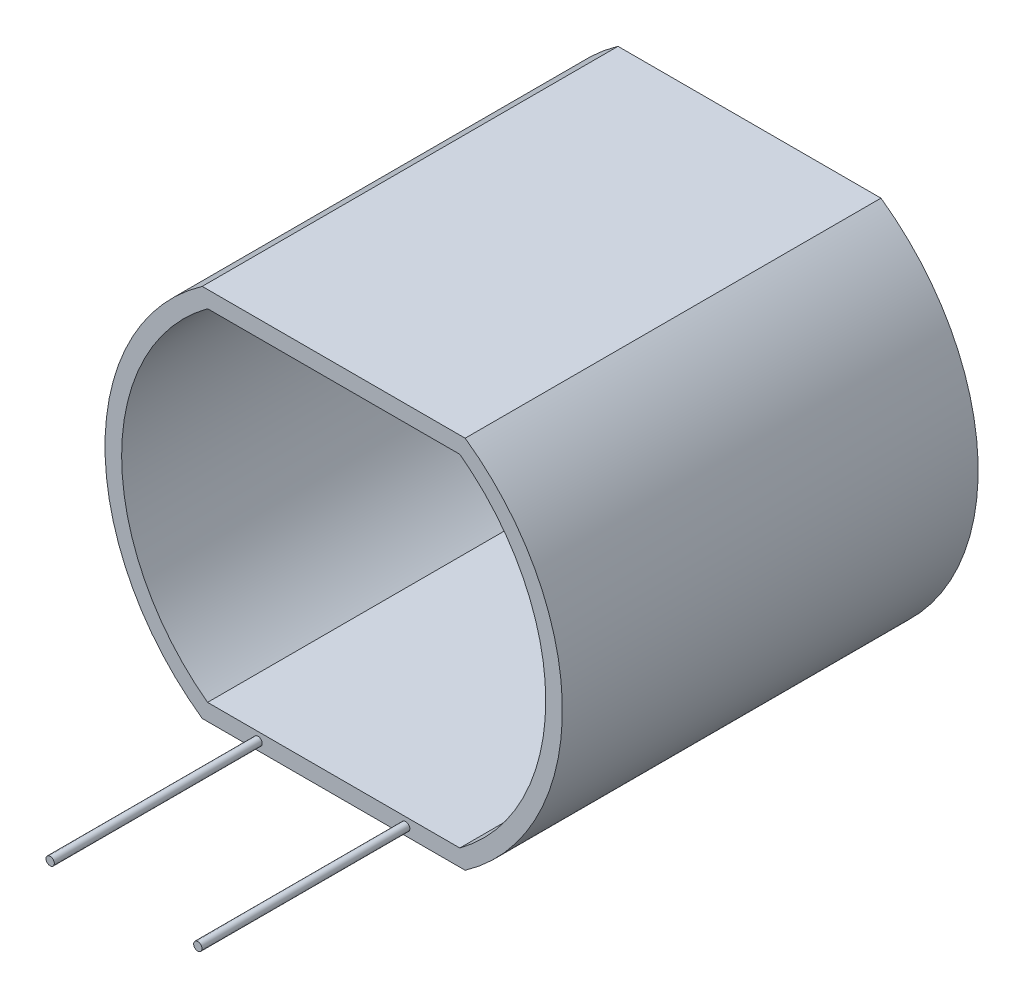
SolidWorks part; units mm, degrees
ref_plane "Front Plane" through (0, 0, 0) normal (0, 0, 1) x (1, 0, 0)
ref_plane "Top Plane" through (0, 0, 0) normal (0, 1, 0) x (1, 0, 0)
ref_plane "Right Plane" through (0, 0, 0) normal (1, 0, 0) x (0, 0, -1)
sketch "Sketch2" plane through (0, 0, 0) normal (0, 0, 1) x (1, 0, 0)
  line L3 (15.8114, 22.5) -> (-15.8114, 22.5)
  line L5 (15.8114, -22.5) -> (-15.8114, -22.5)
  arc A1 (15.8114, -22.5) -> (15.8114, 22.5) centre (0, 0) ccw
  arc A2 (-15.8114, 22.5) -> (-15.8114, -22.5) centre (0, 0) ccw
  circle A3 centre (0, 0) radius 4.75
extrude "Boss-Extrude8" add sketch "Sketch2" along normal blind 50
shell "Shell4" thickness 2 removed face at (4.75, 0, 50) removed face at (0, 0, 50)
sketch "Sketch3" plane through (0, 0, 50) normal (0, 0, 1) x (1, 0, 0)
  circle A0 centre (-9.0964, -21.4937) radius 0.5
  circle A1 centre (8.6571, -21.4937) radius 0.5
  dimension "D1" = 17.7535
extrude "Boss-Extrude9" add sketch "Sketch3" along normal blind 25
